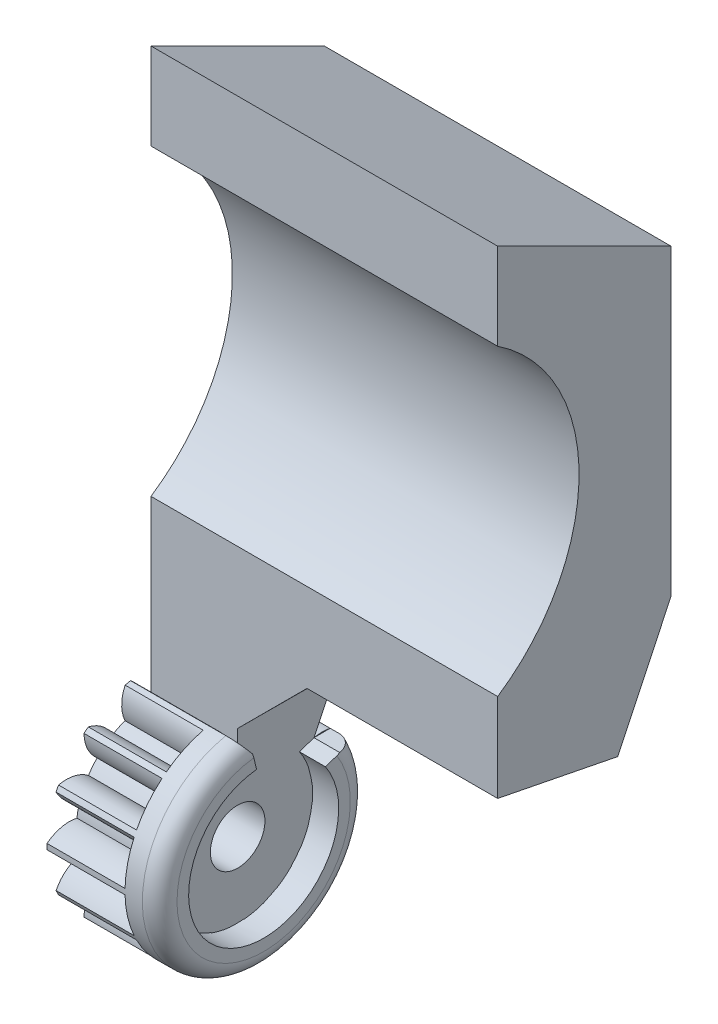
SolidWorks part; units mm, degrees
ref_plane "Plane1" through (0, 0, 0) normal (0, 0, 1) x (1, 0, 0)
ref_plane "Plane2" through (0, 0, 0) normal (0, 1, 0) x (1, 0, 0)
ref_plane "Plane3" through (0, 0, 0) normal (1, 0, 0) x (0, 0, -1)
other "Configuration Table"
sketch "HoldingSke" plane through (0, 0, 0) normal (0, 1, 0) x (1, 0, 0)
  line L0 (0, 0) -> (0.6469, -0.1613)
  line L1 (-15, 0) -> (100, 0) construction
  line L2 (0, 0) -> (-2.1039, 2.3779)
  line L3 (0, 0) -> (-11.863, 4.5341)
  line L4 (0, 0) -> (8.3795, 2.0892)
  line L5 (0, 0) -> (-46.8476, -17.4728)
  line L6 (0, 0) -> (-8.2896, -5.593)
  line L7 (-2.1039, 2.3779) -> (8.6586, 51.2059)
  line L8 (-76.2, 54.61) -> (-75.7, 54.61)
  line L9 (-71.009, 38.7566) -> (-53.1078, 45.2721)
  line L10 (-76.2, 71.12) -> (104.1128, 71.12)
  line L11 (0, 0) -> (-10, 0)
  line L12 (-76.2, 101.6) -> (-76.147, 101.6)
  line L13 (24.9733, 27.94) -> (52.9518, 28.4284)
  line L14 (24.9733, 27.94) -> (24.9743, 27.94)
  line L15 (24.9733, 27.94) -> (100.4006, 29.5858)
  line L16 (-63.627, -1.5) -> (-12.827, -1.5)
  circle A0 centre (0, 0) radius 1.5
  circle A1 centre (0, 0) radius 8.624
  circle A2 centre (0, 0) radius 37.5
  circle A3 centre (0, 0) radius 1.5
  dimension "MHD" = 17.248
  dimension "Hub_dia" = 75
  dimension "Bore" = 3
  dimension "MBD" = 3
  dimension "Num_teeth" = 14
  dimension "Pitch" = 0.6667
  dimension "Overall_len" = 50
  dimension "Show_teeth" = 14
  dimension "Thickness" = 10
  dimension "OAL" = 50.0001
  dimension "T_dim" = 0.5
  dimension "Ap" = 20
  dimension "H" = 19.05
  dimension "Pitch_radius" = 180.3128
  dimension "Width" = 10
  dimension "Backlash" = 0.053
  dimension "Addendum_fac" = 1
  dimension "Dedendum_fac" = 1.25
  dimension "Clearance_fac" = 0.25
  dimension "Dedendum_add" = 0.001
  dimension "Module" = 1.5
sketch "BasProSke" plane through (0, 0, 0) normal (0, 1, 0) x (1, 0, 0)
  line L0 (-10, 0) -> (60, 0) construction
  line L1 (0, 0) -> (0, 12)
  line L2 (0, 0) -> (10, 0)
  line L3 (10, 0) -> (10, 12)
  line L4 (10, 12) -> (0, 12)
  dimension "Thickness" = 10
  dimension "Diameter" = 24
revolve "Base-Revolve" add sketch "BasProSke" angle 360 about L0
sketch "TooCutSke" plane through (0, 0, 0) normal (1, 0, 0) x (0, 0, -1)
  line L1 (0, 0) -> (0, 107) construction
  line L2 (0, 0) -> (-1.2683, 10.4231) construction
  line L3 (0, 0) -> (-4.648, 20.3643) construction
  line L4 (-1.2683, 10.4231) -> (-2.324, 10.1822) construction
  arc A0 (0.8048, 8.5864) -> (-0.8048, 8.5864) centre (0, 0) ccw
  arc A1 (2.3844, 11.7866) -> (-2.3844, 11.7866) centre (0, 0) ccw
  circle A2 centre (0, 0) radius 10.5 construction
  circle A3 centre (0, 0) radius 9.8668 construction
  arc A4 (-0.8048, 8.5864) -> (-2.3844, 11.7866) centre (-5.004, 8.5037) ccw
  arc A5 (2.3844, 11.7866) -> (0.8048, 8.5864) centre (5.004, 8.5037) ccw
  dimension "Root_dia" = 17.248
  dimension "Overcut_dia" = 24.0508
  dimension "Pitch_dia" = 21
  dimension "Base_dia" = 19.7335
  dimension "Flank_rad" = 4.2
  dimension "Half_ang" = 12.857
  dimension "Half_CT" = 1.0829
extrude "ToothCut" cut sketch "TooCutSke" along normal through all
fillet "Breaks" [suppressed] radius 0.03 tangent propagation no
fillet "RootFillets" [suppressed] radius 0.376
pattern_circular "TeethCuts" count 14 every 25.714 about axis through (-10, 0, 0) along (1, 0, 0) of "ToothCut", "RootFillets", "Breaks"
sketch "HubNeaOneSke" plane through (0, 0, 0) normal (-1, 0, 0) x (0, 0, 1)
  circle A0 centre (0, 0) radius 8.624
  dimension "Diameter" = 17.248
extrude "HubNearOne" [suppressed] add sketch "HubNeaOneSke" along normal blind 40.0001
sketch "HubNeaBotSke" plane through (0, 0, 0) normal (-1, 0, 0) x (0, 0, 1)
  circle A0 centre (0, 0) radius 8.624
  dimension "Diameter" = 17.248
extrude "HubNearBoth" [suppressed] add sketch "HubNeaBotSke" along normal blind 20
ref_plane "FarPln" through (10, 0, 0) normal (1, 0, 0) x (0, 0, -1)
sketch "HubFarSke" plane through (10, 0, 0) normal (1, 0, 0) x (0, 0, -1)
  circle A0 centre (0, 0) radius 8.624
  dimension "Diameter" = 17.248
extrude "HubFar" [suppressed] add sketch "HubFarSke" along normal blind 20
sketch "BorSke" plane through (0, 0, 0) normal (1, 0, 0) x (0, 0, -1)
  circle A0 centre (0, 0) radius 1.5
  dimension "Diameter" = 3
extrude "Bore" cut sketch "BorSke" along normal mid plane 100.0001
sketch "KeySke" plane through (0, 0, 0) normal (1, 0, 0) x (0, 0, -1)
  line L0 (-0.6, 0) -> (-0.6, 2)
  line L1 (-0.6, 2) -> (0.6, 2)
  line L2 (0.6, 2) -> (0.6, 0)
  line L3 (0, 0) -> (0, 34) construction
  line L4 (-0.6, 0) -> (0.6, 0)
  dimension "Offset" = 2
  dimension "Width" = 1.2
extrude "Keyway" [suppressed] cut sketch "KeySke" along normal mid plane 100.0001
pattern_circular "Keyway2" [suppressed] count 2 every 90 about axis through (-10, 0, 0) along (1, 0, 0) reverse direction yes
sketch "Sketch1" plane through (10, 0, 0) normal (1, 0, 0) x (0, 0, -1)
  line L3 (0, 1.5) -> (0, 29)
  line L6 (0, 64) -> (0, 29) construction
  line L7 (0, 64) -> (0, 74)
  line L8 (0, 74) -> (20, 64)
  line L9 (20, 64) -> (20, 29)
  line L11 (0, 4) -> (8, 4)
  line L12 (8, 4) -> (20, 29)
  arc A0 (0, 64) -> (0, 29) centre (-11.6082, 46.5) cw
  circle A3 centre (0, 0) radius 1.5 construction
  dimension "D1" = 21
  dimension "D2" = 25
  dimension "D3" = 35
  dimension "D4" = 10
  dimension "D5" = 20
  dimension "D6" = 20
  dimension "D7" = 8
  dimension "D9" = 2.5
extrude "Boss-Extrude1" add sketch "Sketch1" against normal up to surface (10 mm away) contours L7 A0 L3 L11 L12 L9 L8 region at (10, 38.0189, -10.2085) up to face at (0, 0, -1.5)
ref_plane "Plane4" through (-24.9, 0, 0) normal (1, 0, 0) x (0, 0, -1)
sketch "Sketch2" plane through (0, 0, 0) normal (-1, 0, 0) x (0, 0, 1)
  line L2 (0, 29) -> (0, 8.624) construction
  line L3 (-20, 29) -> (-7.6988, 3.1394)
  line L5 (-20, 29) -> (-20, 64) construction
  line L6 (0, 74) -> (0, 64) construction
  line L7 (-20, 64) -> (0, 74) construction
  line L8 (0, 29) -> (0, 8.624)
  line L9 (0, 74) -> (0, 64)
  line L10 (-20, 64) -> (0, 74)
  line L11 (-20, 29) -> (-20, 64)
  line L13 (-20, 29) -> (-6.1505, -0.1156) construction
  line L14 (-7.6988, 3.1394) -> (0, 8.624)
  arc A0 (0, 64) -> (0, 29) centre (11.6082, 46.5) ccw construction
  arc A1 (0, 64) -> (0, 29) centre (11.6082, 46.5) ccw
extrude "Boss-Extrude2" add sketch "Sketch2" against normal blind 40
sketch "Sketch9" plane through (40, 0, 0) normal (1, 0, 0) x (0, 0, -1)
  line L0 (7.6988, 3.1394) -> (0, 8.624)
  line L1 (0, 8.624) -> (0, 18.812)
  line L2 (0, 8.624) -> (0, 29) construction
  line L3 (0, 18.812) -> (13.8494, 16.0697)
  line L4 (20, 29) -> (7.6988, 3.1394) construction
  line L5 (13.8494, 16.0697) -> (7.6988, 3.1394)
extrude "Cut-Extrude5" cut sketch "Sketch9" against normal blind 30
sketch "Sketch10" plane through (10, 0, 0) normal (1, 0, 0) x (0, 0, -1)
  line L0 (0, 18.812) -> (0, 10.812)
  line L1 (0, 18.812) -> (0, 8.624) construction
  line L2 (0, 18.812) -> (15.1538, 18.812)
  line L3 (20, 29) -> (13.8494, 16.0697) construction
  line L7 (0, 10.812) -> (11.3306, 10.7745)
  line L8 (8.8118, 5.4793) -> (13.8494, 16.0697) construction
  line L9 (11.3306, 10.7745) -> (15.1538, 18.812)
  dimension "D1" = 8
extrude "Boss-Extrude5" add sketch "Sketch10" along normal blind 10
chamfer "Chamfer1" distance 10 angle 45 1 edges at (20, 10.7932, -5.6653)
sketch "Sketch11" plane through (10, 0, 0) normal (1, 0, 0) x (0, 0, -1)
  line L0 (-2.3587, 11.7659) -> (-1.2305, 10.3478)
  line L1 (-1.2305, 10.3478) -> (-0.816, 8.6189)
  line L2 (7.1252, 4.9177) -> (8.8118, 5.4793)
  line L3 (8.8118, 5.4793) -> (10.6696, 5.4918)
  arc A0 (10.6696, 5.4918) -> (-2.3587, 11.7659) centre (0, 0) cw
  arc A1 (-2.3587, 11.7659) -> (-2.98, 11.6241) centre (0, 0) ccw construction
  arc A2 (7.1252, 4.9177) -> (-0.816, 8.6189) centre (0, 0) cw
  arc A3 (-0.8048, 8.5864) -> (-2.3587, 11.7659) centre (-5.004, 8.5037) ccw construction
extrude "Boss-Extrude6" add sketch "Sketch11" along normal blind 3 and the other way blind 1
fillet "Fillet1" radius 2 1 edges at (13, -10.8116, 5.2066)
sketch "Sketch12" plane through (0, 0, 0) normal (-1, 0, 0) x (0, 0, 1)
  circle A0 centre (0, 0) radius 3.15
  dimension "D1" = 6.3
extrude "Cut-Extrude6" cut sketch "Sketch12" against normal through all
equation "' \"Module@HoldingSke\" = 6.35"
equation "' \"Num_teeth@HoldingSke\" = 12"
equation "' \"Ap@HoldingSke\" =  20"
equation "' \"Ap@HoldingSke\" = 20"
equation "' \"Width@HoldingSke\" = 0.5 * 25.4"
equation "' \"Hub_dia@HoldingSke\"= 1 * 25.4"
equation "' \"Hub_dia@HoldingSke\" = 1 * 25.4"
equation "' \"Overall_len@HoldingSke\" = 1.0 * 25.4"
equation "' \"Bore@HoldingSke\" = 0.75 * 25.4"
equation "' \"T_dim@HoldingSke\" = 0.1 * 25.4"
equation "' \"Width@KeySke\" = 0.25 * 25.4"
equation "' \"Show_teeth@HoldingSke\" = 13"
equation "' \"Backlash@HoldingSke\" = 0.009 * 25.4"
equation "' \"Addendum_fac@HoldingSke\" = 1.0"
equation "' \"Dedendum_fac@HoldingSke\" = 1.25"
equation "' \"Dedendum_add@HoldingSke\" = 0.00005 * 25.4"
equation "' \"Clearance_fac@HoldingSke\" = 0.25"
equation "\"Pitch@HoldingSke\" = 1 / \"Module@HoldingSke\""
equation "\"Overcut_dia@TooCutSke\" = (\"Num_teeth@HoldingSke\" + 2 * \"Addendum_fac@HoldingSke\") / \"Pitch@HoldingSke\" + 0.002 * 25.4"
equation "\"Pitch_dia@TooCutSke\" = \"Num_teeth@HoldingSke\" / \"Pitch@HoldingSke\""
equation "\"Base_dia@TooCutSke\" = \"Num_teeth@HoldingSke\" / \"Pitch@HoldingSke\" * cos((\"Ap@HoldingSke\"  * 3.14159265 / 180))"
equation "\"Root_dia@TooCutSke\" = (\"Num_teeth@HoldingSke\" + 2) / \"Pitch@HoldingSke\" - 2 * (\"Addendum_fac@HoldingSke\" + \"Dedendum_fac@HoldingSke\") / \"Pitch@HoldingSke\" - \"Dedendum_add@HoldingSke\" * 2"
equation "\"Half_ang@TooCutSke\" = 180 / \"Num_teeth@HoldingSke\""
equation "\"Half_CT@TooCutSke\" = \"Num_teeth@HoldingSke\" / \"Pitch@HoldingSke\" * sin((3.14159265 / 2 / \"Num_teeth@HoldingSke\")) / 2 - 7 * \"Backlash@HoldingSke\" / 4"
equation "\"Flank_rad@TooCutSke\" = \"Num_teeth@HoldingSke\" / \"Pitch@HoldingSke\" / 5"
equation "\"Radius@RootFillets\" = \"Clearance_fac@HoldingSke\" / \"Pitch@HoldingSke\" + \"Dedendum_add@HoldingSke\""
equation "\"Break_rad@Breaks\" = 0.02 / \"Pitch@HoldingSke\""
equation "\"Thickness@HoldingSke\" = \"Width@HoldingSke\""
equation "\"OAL@HoldingSke\" = \"Thickness@HoldingSke\""
equation "\"MHD@HoldingSke\" = (\"Num_teeth@HoldingSke\" + 2) / \"Pitch@HoldingSke\" - 2 * (\"Addendum_fac@HoldingSke\" + \"Dedendum_fac@HoldingSke\")  / \"Pitch@HoldingSke\" - \"Dedendum_add@HoldingSke\" * 2"
equation "\"MBD@HoldingSke\" = (\"Num_teeth@HoldingSke\" + 2) / \"Pitch@HoldingSke\" - 2 * (\"Addendum_fac@HoldingSke\" + \"Dedendum_fac@HoldingSke\")  / \"Pitch@HoldingSke\" - \"Dedendum_add@HoldingSke\" * 2 - 0.002 * 25.4"
equation "\"MHD@HoldingSke\" = ((sgn( \"MHD@HoldingSke\" - \"Hub_dia@HoldingSke\" )-1)*( \"MHD@HoldingSke\" - \"Hub_dia@HoldingSke\" ))/-2+ \"Hub_dia@HoldingSke\""
equation "\"MBD@HoldingSke\" = ((sgn( \"MBD@HoldingSke\" - \"Bore@HoldingSke\" )-1)*( \"MBD@HoldingSke\" - \"Bore@HoldingSke\" ))/-2+ \"Bore@HoldingSke\""
equation "\"OAL@HoldingSke\" = ((sgn( \"OAL@HoldingSke\" - \"Overall_len@HoldingSke\" )+1)*( \"OAL@HoldingSke\" - \"Overall_len@HoldingSke\" ))/2 + \"Overall_len@HoldingSke\" + 0.000002 * 25.4"
equation "\"Num_teeth@TeethCuts\" = int( \"Show_teeth@HoldingSke\" ) + 1"
equation "\"Num_teeth@TeethCuts\" = ((sgn( \"Num_teeth@TeethCuts\" - \"Num_teeth@HoldingSke\" )-1)*( \"Num_teeth@TeethCuts\" - \"Num_teeth@HoldingSke\" ))/-2+ \"Num_teeth@HoldingSke\""
equation "\"Num_teeth@TeethCuts\" = ((sgn( \"Num_teeth@TeethCuts\" - 2.0)+1)*( \"Num_teeth@TeethCuts\" - 2.0))/2 +2.0"
equation "\"Angle@TeethCuts\" = 360.0 / \"Num_teeth@HoldingSke\""
equation "\"Diameter@BasProSke\" = (\"Num_teeth@HoldingSke\" + 2 * \"Addendum_fac@HoldingSke\") / \"Pitch@HoldingSke\""
equation "\"Thickness@BasProSke\"  = \"Thickness@HoldingSke\""
equation "' \"Fillet_rad@BasProSke\" =  \"Thickness@HoldingSke\" * 0.05"
equation "' \"Fillet_rad@BasProSke\" = \"Thickness@HoldingSke\" * 0.05"
equation "\"MHD@HoldingSke\" = ((sgn( \"MHD@HoldingSke\" - \"Root_dia@TooCutSke\" )-1)*( \"MHD@HoldingSke\" - \"Root_dia@TooCutSke\" ))/-2+ \"Root_dia@TooCutSke\""
equation "\"Diameter@HubNeaOneSke\" = \"MHD@HoldingSke\""
equation "\"Length@HubNearOne\" = \"OAL@HoldingSke\" - \"Thickness@BasProSke\""
equation "\"Diameter@HubNeaBotSke\" = \"MHD@HoldingSke\""
equation "\"Length@HubNearBoth\" = ( \"OAL@HoldingSke\" - \"Thickness@BasProSke\" ) / 2.0"
equation "\"Thickness@FarPln\" = \"Thickness@BasProSke\""
equation "\"Diameter@HubFarSke\" = \"MHD@HoldingSke\""
equation "\"Length@HubFar\" = ( \"OAL@HoldingSke\" - \"Thickness@BasProSke\" ) / 2.0"
equation "\"Diameter@BorSke\" = \"MBD@HoldingSke\""
equation "\"D1@Bore\" = \"OAL@HoldingSke\" * 2.0"
equation "\"D1@Keyway\" = \"OAL@HoldingSke\" * 2.0"
equation "\"Offset@KeySke\" = \"T_dim@HoldingSke\" + \"MBD@HoldingSke\" / 2.0"
